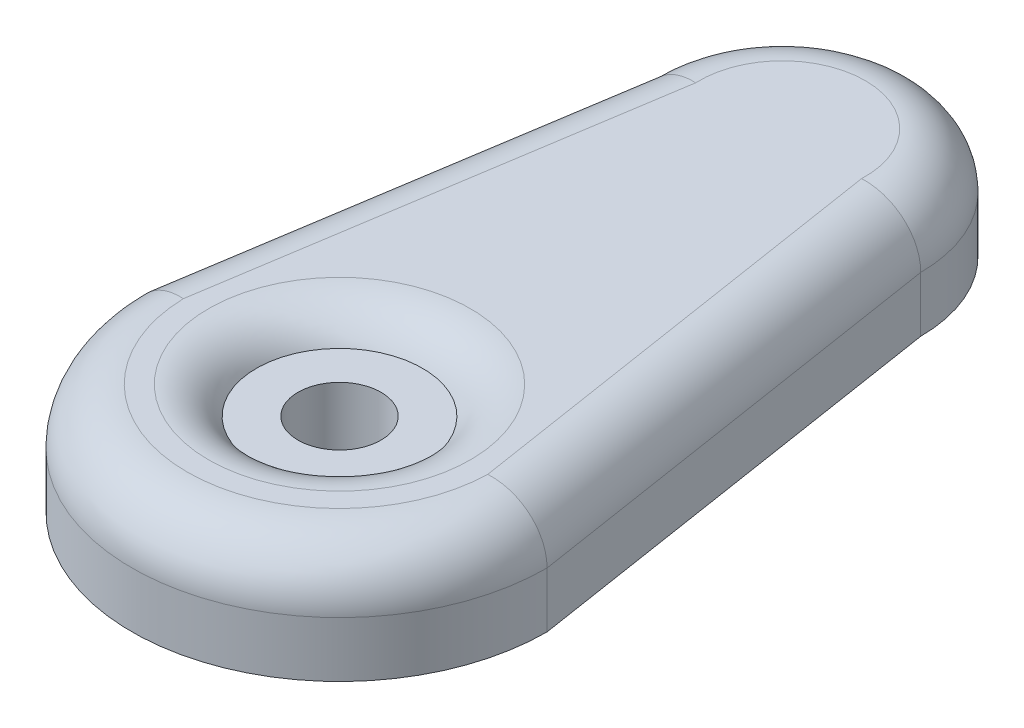
SolidWorks part; units mm, degrees
ref_plane "Front Plane" through (0, 0, 0) normal (0, 0, 1) x (1, 0, 0)
ref_plane "Top Plane" through (0, 0, 0) normal (0, 1, 0) x (1, 0, 0)
ref_plane "Right Plane" through (0, 0, 0) normal (1, 0, 0) x (0, 0, -1)
sketch "Sketch2" plane through (0, 0, 0) normal (0, 1, 0) x (1, 0, 0)
  line L0 (-3.75, 0) -> (-2.5, 8)
  line L1 (2.5, 8) -> (3.75, 0)
  circle A0 centre (0, 0) radius 0.75
  arc A1 (-3.75, 0) -> (3.75, 0) centre (0, 0) ccw
  arc A2 (2.5, 8) -> (-2.5, 8) centre (0, 8) ccw
  dimension "D1" = 1.5
  dimension "D2" = 3
  dimension "D4" = 5
  dimension "D3" = 8
extrude "Boss-Extrude1" add sketch "Sketch2" along normal blind 2
sketch "Sketch3" plane through (0, 2, 0) normal (0, 1, 0) x (1, 0, 0)
  circle A0 centre (0, 0) radius 1.5
  dimension "D1" = 3
extrude "Cut-Extrude1" cut sketch "Sketch3" against normal blind 0.5
fillet "Fillet1" radius 1 5 edges at (0, 2, 1.5) (0, 2, -10.5) (3.125, 2, -4) (0, 2, 3.75) (-3.125, 2, -4)
